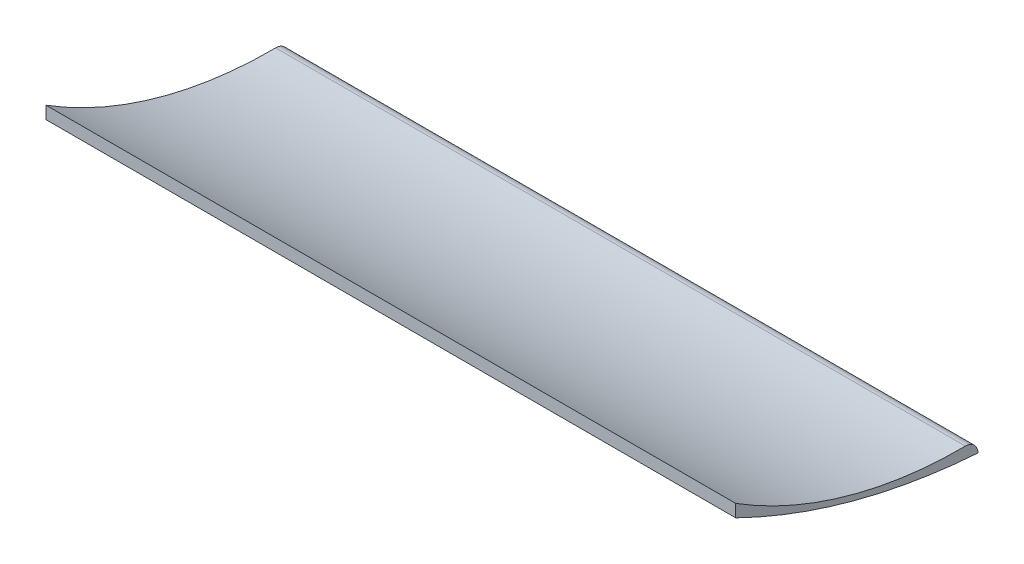
SolidWorks part; units mm, degrees
material "Rubber"
ref_plane "Front Plane" through (0, 0, 0) normal (0, 0, 1) x (1, 0, 0)
ref_plane "Top Plane" through (0, 0, 0) normal (0, 1, 0) x (1, 0, 0)
ref_plane "Right Plane" through (0, 0, 0) normal (1, 0, 0) x (0, 0, -1)
sketch "Sketch1" plane through (0, 0, 0) normal (1, 0, 0) x (0, 0, -1)
  line L0 (0, 0) -> (193.1852, -51.7638) construction
  line L1 (0, 0) -> (32.6753, 0) construction
  line L2 (193.1852, -51.7638) -> (193.1852, -41.7638)
  line L4 (0, 10) -> (0, 0)
  arc A0 (0, 10) -> (193.1852, -41.7638) centre (180.6988, 298.0068) ccw
  arc A1 (0, 0) -> (193.1852, -51.7638) centre (228.6664, 467.0243) ccw
  dimension "D3" = 340
  dimension "D4" = 520
  dimension "D1" = 200
  dimension "D2" = 15
  dimension "D5" = 10
extrude "Boss-Extrude1" add sketch "Sketch1" along normal blind 550
fillet "Fillet1" radius 10 1 edges at (275, -41.7638, -193.1852)
ref_plane "Plane1" through (275, 0, 0) normal (1, 0, 0) x (0, 0, -1)
